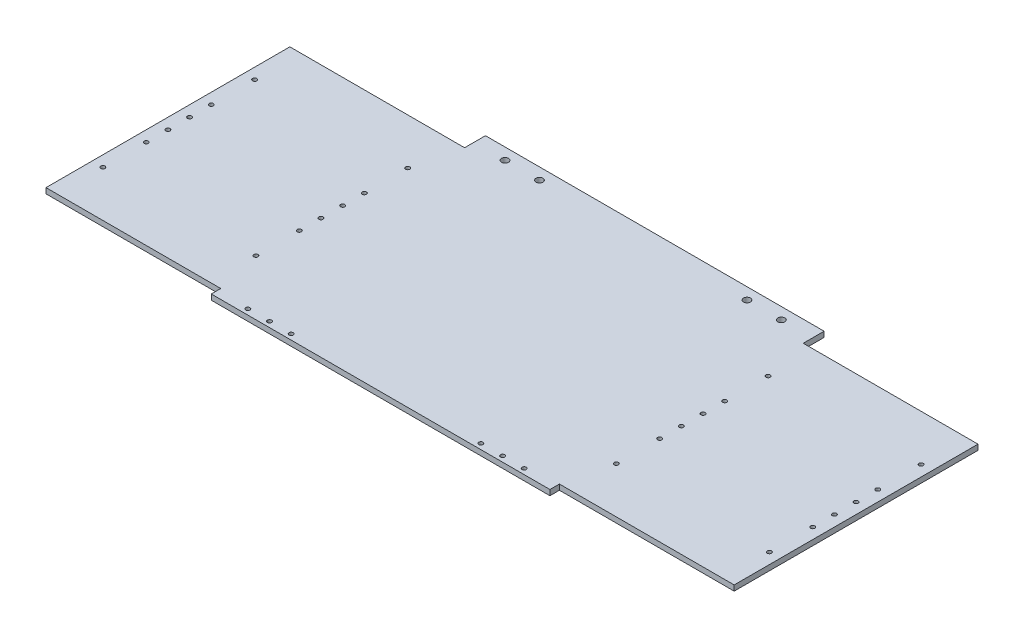
SolidWorks part; units mm, degrees
ref_plane "Front Plane" through (0, 0, 0) normal (0, 0, 1) x (1, 0, 0)
ref_plane "Top Plane" through (0, 0, 0) normal (0, 1, 0) x (1, 0, 0)
ref_plane "Right Plane" through (0, 0, 0) normal (1, 0, 0) x (0, 0, -1)
sketch "Sketch1" plane through (0, 0, 0) normal (0, 1, 0) x (1, 0, 0)
  line L0 (129, 0) -> (129, -7)
  line L1 (0, 0) -> (129, 0)
  line L2 (0, 0) -> (0, 180)
  line L3 (0, 180) -> (129, 180)
  line L4 (508, 0) -> (508, 180)
  line L5 (129, -7) -> (379, -7)
  line L6 (379, -7) -> (379, 0)
  line L7 (0, 90) -> (508, 90) construction
  line L8 (129, 180) -> (129, 195.398)
  line L9 (129, 195.398) -> (379, 195.398)
  line L10 (379, 195.398) -> (379, 180)
  line L11 (254, 195.398) -> (254, -38.1) construction
  line L12 (379, 0) -> (508, 0)
  line L13 (379, 180) -> (508, 180)
  line L14 (129, 186.858) -> (379, 186.858) construction
  line L15 (129, -3) -> (254, -3) construction
  circle A0 centre (152, 186.858) radius 2.564
  circle A1 centre (177.4, 186.858) radius 2.564
  circle A4 centre (152, -3) radius 1.55
  circle A5 centre (184, -3) radius 1.55
  circle A8 centre (330.6, 186.858) radius 2.564
  circle A9 centre (356, 186.858) radius 2.564
  circle A10 centre (168, -3) radius 1.55
  circle A11 centre (324, -3) radius 1.55
  circle A12 centre (340, -3) radius 1.55
  circle A13 centre (356, -3) radius 1.55
  circle A14 centre (121, 146) radius 1.55
  circle A15 centre (121, 114) radius 1.55
  circle A16 centre (121, 98) radius 1.55
  circle A17 centre (121, 82) radius 1.55
  circle A18 centre (121, 66) radius 1.55
  circle A19 centre (121, 34) radius 1.55
  circle A20 centre (387, 146) radius 1.55
  circle A21 centre (387, 114) radius 1.55
  circle A22 centre (387, 98) radius 1.55
  circle A23 centre (387, 82) radius 1.55
  circle A24 centre (387, 66) radius 1.55
  circle A25 centre (387, 34) radius 1.55
  circle A26 centre (8, 146) radius 1.55
  circle A27 centre (8, 114) radius 1.55
  circle A28 centre (8, 98) radius 1.55
  circle A29 centre (8, 82) radius 1.55
  circle A30 centre (8, 66) radius 1.55
  circle A31 centre (8, 34) radius 1.55
  circle A32 centre (500, 34) radius 1.55
  circle A33 centre (500, 66) radius 1.55
  circle A34 centre (500, 82) radius 1.55
  circle A35 centre (500, 98) radius 1.55
  circle A36 centre (500, 114) radius 1.55
  circle A37 centre (500, 146) radius 1.55
  point P10 (254, 90)
  point P72 (0, 0)
  dimension "D7" = 3.1
  dimension "D9" = 5.128
  dimension "D16" = 3.1
  dimension "D21" = 3.1
  dimension "D1" = 180
  dimension "D2" = 508
  dimension "D3" = 250
  dimension "D5" = 250
  dimension "D8" = 8.54
  dimension "D10" = 25.4
  dimension "D11" = 23
  dimension "D6" = 6.858
  dimension "D12" = 16
  dimension "D13" = 16
  dimension "D14" = 23
  dimension "D15" = 4
  dimension "D4" = 3
  dimension "D17" = 32
  dimension "D19" = 16
  dimension "D20" = 8
  dimension "D18" = 8
  dimension "D22" = 8
  dimension "D23" = 16
  dimension "D24" = 32
  dimension "D25" = 8
extrude "Boss-Extrude1" add sketch "Sketch1" along normal blind 4
equation "\"cf_tube_outer_diameter\"= 25mm"
equation "\"cf_tube_inner_diameter\" = 21mm"
equation "\"mid_plate_mid_to_top\" = 100mm"
equation "\"mid_plate_mid_to_bottom\" = 30mm"
equation "\"mid_plate_horizontal_spacing\"=250mm"
equation "\"cf_plate_thickness\" =4mm"
equation "\"mid_tube_length\" = 121mm"
equation "\"mid_plate_bottom_width\" = 180mm"
equation "\"D1@Sketch1\"=\"mid_plate_bottom_width\""
equation "\"D1@Boss-Extrude1\"=\"cf_plate_thickness\""
equation "\"D5@Sketch1\"=\"mid_plate_horizontal_spacing\""
equation "\"D3@Sketch1\"=\"mid_plate_horizontal_spacing\""
